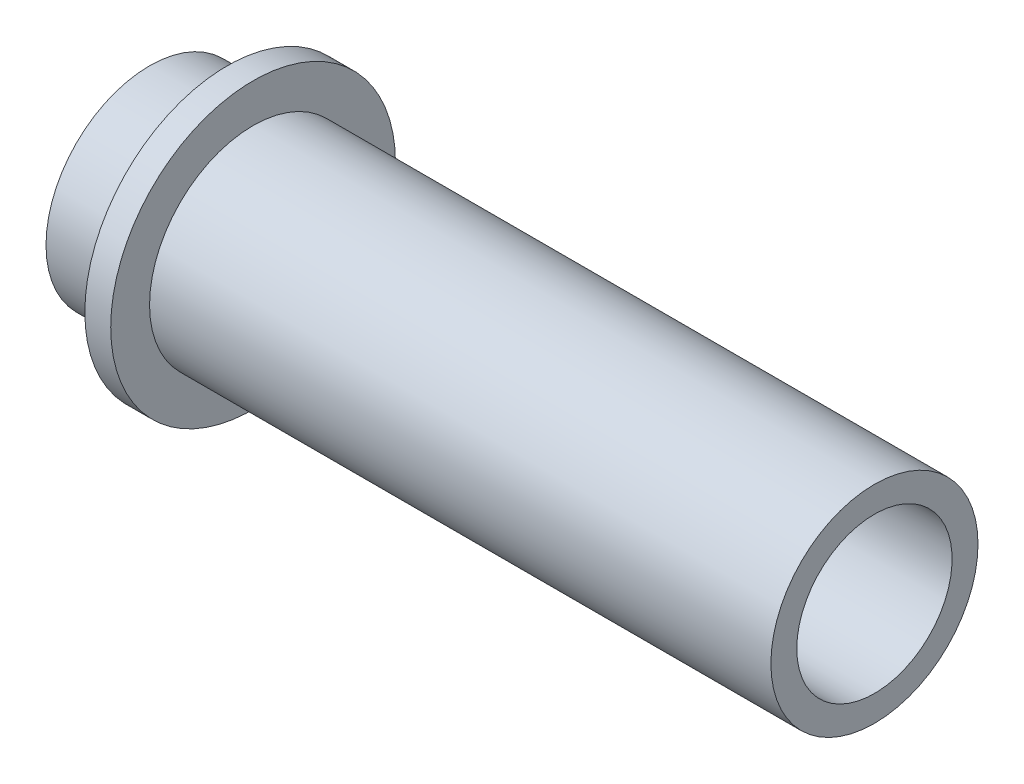
SolidWorks part; units mm, degrees
ref_plane "Front Plane" through (0, 0, 0) normal (0, 0, 1) x (1, 0, 0)
ref_plane "Top Plane" through (0, 0, 0) normal (0, 1, 0) x (1, 0, 0)
ref_plane "Right Plane" through (0, 0, 0) normal (1, 0, 0) x (0, 0, -1)
sketch "Sketch1" plane through (0, 0, 0) normal (1, 0, 0) x (0, 0, -1)
  circle A0 centre (0, 0) radius 8.7312
  dimension "D1" = 17.4625
extrude "Boss-Extrude1" add sketch "Sketch1" along normal blind 1.5875
sketch "Sketch2" plane through (1.5875, 0, 0) normal (1, 0, 0) x (0, 0, -1)
  circle A0 centre (0, 0) radius 6.35
  dimension "D1" = 12.7
extrude "Boss-Extrude2" add sketch "Sketch2" along normal blind 38.1
sketch "Sketch4" plane through (0, 0, 0) normal (-1, 0, 0) x (0, 0, 1)
  circle A0 centre (0, 0) radius 6.35
  dimension "D1" = 12.7
extrude "Boss-Extrude3" add sketch "Sketch4" along normal blind 4.7625
sketch "Sketch5" plane through (-4.7625, 0, 0) normal (-1, 0, 0) x (0, 0, 1)
  circle A0 centre (0, 0) radius 4.7625
  dimension "D1" = 9.525
extrude "Cut-Extrude1" cut sketch "Sketch5" against normal through all contours A0
